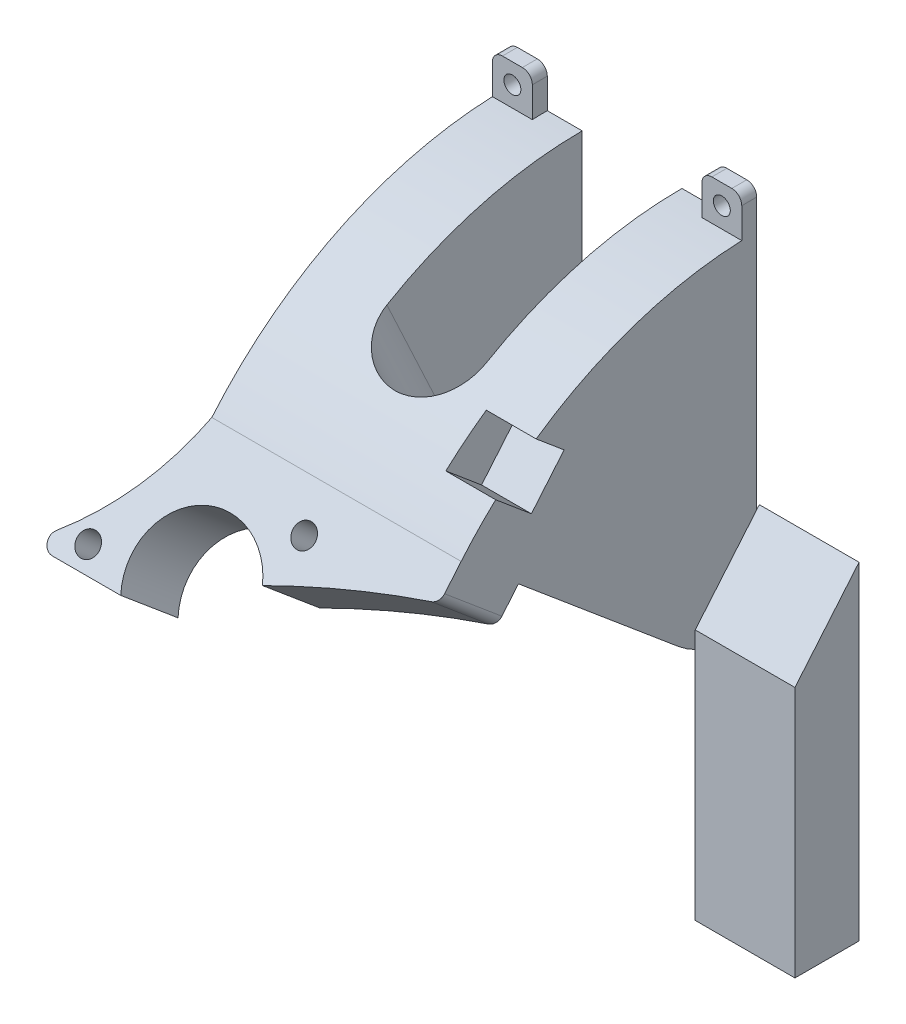
SolidWorks part; units mm, degrees
ref_plane "Ebene vorne" through (0, 0, 0) normal (0, 0, 1) x (1, 0, 0)
ref_plane "Ebene oben" through (0, 0, 0) normal (0, 1, 0) x (1, 0, 0)
ref_plane "Ebene rechts" through (0, 0, 0) normal (1, 0, 0) x (0, 0, -1)
sketch "Skizze1" plane through (0, 0, 0) normal (1, 0, 0) x (0, 0, -1)
  line L0 (0, 0) -> (0, 65.7804)
  line L1 (0, 0) -> (-12.8558, 0)
  line L2 (-12.8558, 0) -> (-12.8558, 50.4596)
  line L3 (-12.8558, 50.4596) -> (0, 65.7804)
  line L4 (-6.4279, 0) -> (-6.4279, 58.12) construction
  dimension "D1" = 50
  dimension "D2" = 20
  dimension "D3" = 58.12
extrude "Aufsatz-Linear austragen1" add sketch "Skizze1" along normal blind 20
ref_plane "Ebene1" through (0, 38.6015, -32.3905) normal (0, 0.766, -0.6428) x (-1, 0, 0)
sketch "Skizze2" plane through (0, 38.6015, -32.3905) normal (0, 0.766, -0.6428) x (-1, 0, 0)
  line L0 (-20, 42.2829) -> (0, 42.2829) construction
  line L1 (-10, 0) -> (-10, 83.3321) construction
  line L2 (-20, 0) -> (0, 0) construction
  line L3 (90, 60.5809) -> (90, 32.1579)
  line L4 (90, 32.1579) -> (40, 32.1579)
  line L5 (-110, 60.5809) -> (-110, 32.1579)
  line L6 (-60, 38.8503) -> (-60, 32.1579)
  line L7 (40, 38.8503) -> (40, 32.1579)
  line L8 (-60, 32.1579) -> (-110, 32.1579)
  arc A0 (-10, 42.2829) -> (98.0877, 78.3487) centre (-10, 222.2829) ccw construction
  arc A1 (-110, 60.5809) -> (-60, 38.8503) centre (-10, 222.2829) ccw
  arc A2 (40, 38.8503) -> (90, 60.5809) centre (-10, 222.2829) ccw
  point P15 (-10, 22.2829)
  dimension "D1" = 180
  dimension "D3" = 10.125
  dimension "D2" = 200
  dimension "D5" = 100
extrude "Aufsatz-Linear austragen2" add sketch "Skizze2" against normal blind 20
sketch "Skizze4" plane through (-90, 0, 0) normal (-1, 0, 0) x (0, 0, 1)
  line L0 (-7.7562, 59.2722) -> (14.0171, 77.5422) construction
  line L1 (-77.0542, 0) -> (77.0542, 0) construction
  line L2 (5.0996, 43.9513) -> (41.9791, 0)
  line L3 (5.0996, 43.9513) -> (-7.7562, 59.2722) construction
  line L4 (5.0996, 43.9513) -> (-7.7562, 59.2722)
  line L5 (-35.3953, 0) -> (-35.3953, 52.2205) construction
  line L6 (-35.3953, 0) -> (41.9791, 0)
  arc A0 (-7.7562, 59.2722) -> (-35.3953, 0) centre (41.9791, 0) ccw
  point P7 (0, 0)
  line M3 (-7.7562, 59.2722) -> (5.0996, 43.9513)
extrude "Aufsatz-Linear austragen3" add sketch "Skizze4" against normal blind 50 contours A0 L6 L2 M3 region at (-90, 21.1147, -3.3015)
sketch "Skizze6" plane through (0, 38.6015, -32.3905) normal (0, 0.766, -0.6428) x (1, 0, 0)
  line L0 (-90, -60.5809) -> (-109.0162, -60.5809)
  line L1 (-90, -32.1579) -> (-137.6907, -32.1579) construction
  line L2 (-90, -60.5809) -> (-90, -32.1579)
  line L3 (60, -32.1579) -> (-40, -32.1579) construction
  line L4 (10, -32.1579) -> (10, -107.2086) construction
  line L5 (-40, -38.8503) -> (-40, -32.1579)
  line L6 (-40, -32.1579) -> (-90, -32.1579)
  line L7 (-90, -32.1579) -> (-90, -60.5809)
  line L8 (-40, -38.8503) -> (-40, -32.1579)
  line L9 (-40, -32.1579) -> (-90, -32.1579)
  line L10 (110, -60.5809) -> (110, -32.1579)
  line L11 (110, -60.5809) -> (129.0162, -60.5809)
  arc A0 (-90, -32.1579) -> (-109.0162, -60.5809) centre (-144.3179, -16.3897) cw
  arc A1 (110, -32.1579) -> (129.0162, -60.5809) centre (164.3179, -16.3897) ccw
  arc A2 (-40, -38.8503) -> (-90, -60.5809) centre (10, -222.2829) ccw
  arc A3 (-40, -38.8503) -> (-90, -60.5809) centre (10, -222.2829) ccw
  line M9 (-90, -32.1579) -> (-90, -60.5809)
  dimension "D1" = 0
extrude "Aufsatz-Linear austragen4" add sketch "Skizze6" against normal blind 20 contours A0 L0 M9 | A1 L10 L11 region at (-95.6771, 72.2232, 7.6782) region at (115.6771, 72.2232, 7.6782)
fillet "Verrundung1" [suppressed] radius 3
sketch "Skizze5" plane through (0, 38.6015, -32.3905) normal (0, 0.766, -0.6428) x (1, 0, 0)
  line L0 (-79.5999, -54.5945) -> (-69.0166, -48.9382) construction
  line L1 (-79.5999, -54.5945) -> (-90.1831, -60.2508) construction
  line L2 (-79.5999, -54.5945) -> (-86.3975, -41.8758) construction
  line L3 (60, -32.1579) -> (-40, -32.1579) construction
  line L4 (10, -32.1579) -> (10, -101.6812) construction
  arc A0 (-90, -60.5809) -> (-68.8428, -49.2761) centre (-79.5999, -54.5945) cw
  arc A1 (-40, -38.8503) -> (-90, -60.5809) centre (10, -222.2829) ccw construction
  circle A2 centre (-67.9368, -39.2902) radius 2.25
  circle A3 centre (-98.8047, -55.7878) radius 2.25
  arc A4 (-40, -38.8503) -> (-90, -60.5809) centre (10, -222.2829) ccw construction
  arc A5 (110, -60.5809) -> (88.8428, -49.2761) centre (99.5999, -54.5945) ccw
  arc A6 (-90, -60.5809) -> (-68.8428, -49.2761) centre (-79.5999, -54.5945) ccw
  arc A7 (110, -60.5809) -> (88.8428, -49.2761) centre (99.5999, -54.5945) cw
  arc M4 (-90, -60.5809) -> (-40, -38.8503) centre (10, -222.2829) cw
  dimension "D1" = 12
  dimension "D5" = 4.5
  dimension "D2" = 0.38
  dimension "D3" = 35
  dimension "D4" = 8
extrude "Schnitt-Linear austragen1" cut sketch "Skizze5" against normal through all contours A0 M4 | A7 A5 region at (-81.9676, 70.8459, 6.0367) region at (99.5999, 73.6942, 9.4313)
sketch "Skizze7" plane through (60, 0, 0) normal (1, 0, 0) x (0, 0, -1)
  line L0 (7.7562, 59.2722) -> (-41.9791, 0)
  line L1 (-41.9791, 0) -> (35.3953, 0)
  arc A0 (7.7562, 59.2722) -> (35.3953, 0) centre (-41.9791, 0) cw
  arc A2 (35.3953, 0) -> (7.7562, 59.2722) centre (-41.9791, 0) ccw construction
extrude "Aufsatz-Linear austragen5" add sketch "Skizze7" along normal up to vertex (50 mm away) up to point (110, 43.9513, 5.0995)
ref_plane "Ebene5" [suppressed] through (10, 0, 0) normal (1, 0, 0) x (0, 0, -1)
sketch "Skizze9" plane through (0, 38.6015, -32.3905) normal (0, 0.766, -0.6428) x (1, 0, 0)
  line L0 (-55, -32.1579) -> (-55, -43.6141)
  line L1 (-40, -32.1579) -> (-90, -32.1579) construction
  line L2 (-40, -38.8503) -> (-40, -32.1579) construction
  line L6 (-109.0162, -60.5809) -> (-90, -60.5809)
  line L7 (-40, -38.8503) -> (-40, -32.1579)
  line L8 (-40, -32.1579) -> (-90, -32.1579)
  line L9 (-109.0162, -60.5809) -> (-90, -60.5809)
  line L11 (-55, -32.1579) -> (-90, -32.1579)
  arc A0 (-40, -38.8503) -> (-68.8428, -49.2761) centre (10, -222.2829) ccw construction
  arc A4 (-68.8428, -49.2761) -> (-90, -60.5809) centre (-79.5999, -54.5945) ccw
  arc A5 (-40, -38.8503) -> (-68.8428, -49.2761) centre (10, -222.2829) ccw
  arc A6 (-109.0162, -60.5809) -> (-90, -32.1579) centre (-144.3179, -16.3897) ccw
  arc A7 (-68.8428, -49.2761) -> (-90, -60.5809) centre (-79.5999, -54.5945) ccw
  arc A8 (-55, -43.6141) -> (-68.8428, -49.2761) centre (10, -222.2829) ccw
  arc A9 (-109.0162, -60.5809) -> (-90, -32.1579) centre (-144.3179, -16.3897) ccw
  dimension "D1" = 15
  dimension "D2" = 0
extrude "Aufsatz-Linear austragen6" [suppressed] add sketch "Skizze9" along normal blind 6
fillet "Verrundung2" [suppressed] radius 6
fillet "Verrundung3" radius 2 1 edges at (-109.0162, 69.8818, 20.445)
fillet "Verrundung4" [suppressed] radius 1
sketch "Skizze11" plane through (0, 23.2807, -19.5348) normal (0, -0.766, 0.6428) x (1, 0, 0)
  line L0 (60, 32.1579) -> (110, 32.1579)
  line L1 (110, 32.1579) -> (141.0282, 65.9)
  line L2 (141.0282, 65.9) -> (38.3436, 62.9928)
  line L3 (38.3436, 62.9928) -> (60, 32.1579)
  line L4 (-90, 32.1579) -> (-40, 32.1579)
  line L5 (-40, 32.1579) -> (-27.2753, 44.0032)
  line L6 (-27.2753, 44.0032) -> (-71.113, 77.6284)
  line L7 (-71.113, 77.6284) -> (-115.715, 75.5442)
  line L8 (-115.715, 75.5442) -> (-104.047, 34.6918)
  line L9 (-104.047, 34.6918) -> (-90, 32.1579)
extrude "Schnitt-Linear austragen3" cut sketch "Skizze11" against normal blind 5
ref_plane "Ebene6" through (0, 16.6209, -35.6436) normal (0, 0.4226, -0.9063) x (-1, 0, 0)
sketch "Skizze12" plane through (0, 16.6209, -35.6436) normal (0, 0.4226, -0.9063) x (-1, 0, 0)
  line L0 (75, -14.9587) -> (75, 35.0413)
  line L1 (40, -14.9587) -> (90, -14.9587) construction
  line L2 (75, 35.0413) -> (55, 35.0413)
  line L3 (55, 35.0413) -> (55, -14.9587)
  line L4 (55, -14.9587) -> (75, -14.9587)
  line L5 (40, 50.441) -> (40, -14.9587) construction
  line L6 (90, -14.9587) -> (90, 50.441) construction
  line L7 (40, -14.9587) -> (-60, -14.9587) construction
  line L8 (-10, -14.9587) -> (-10, 52.6156) construction
  line L9 (-75, -14.9587) -> (-95, -14.9587)
  line L10 (-75, 35.0413) -> (-75, -14.9587)
  line L11 (-95, -14.9587) -> (-95, 35.0413)
  line L12 (-95, 35.0413) -> (-75, 35.0413)
  dimension "D1" = 15
  dimension "D2" = 15
  dimension "D3" = 50
extrude "Schnitt-Linear austragen4" cut sketch "Skizze12" against normal through all
fillet "Verrundung5" radius 10 2 edges at (75, 39.4549, -1.6965) (95, 39.4549, -1.6965) tangent propagation no
fillet "Verrundung6" radius 10 2 edges at (-55, 39.4549, -1.6965) (-75, 39.4549, -1.6965)
sketch "Skizze13" plane through (0, 0, 0) normal (0, 1, 0) x (1, 0, 0)
  line L0 (-40, 35.3953) -> (-40, 43.3953)
  line L1 (-40, 43.3953) -> (-48, 43.3953)
  line L2 (-44, 39.3953) -> (-44, 35.3953) construction
  line L3 (-51.9152, 39.3953) -> (-40, 39.3953) construction
  line L4 (-40, 35.3953) -> (-55, 35.3953) construction
  line L5 (-48, 35.3953) -> (-48, 43.3953)
  line L6 (-55, 35.3953) -> (-75, 35.3953) construction
  line L7 (-65, 35.3953) -> (-65, 48.5338) construction
  line L8 (60, 35.3953) -> (-40, 35.3953) construction
  line L9 (10, 35.3953) -> (10, 91.6227) construction
  line L10 (-40, 35.3953) -> (-40, 33.3959)
  line L11 (-40, 35.3953) -> (-40, -41.9791) construction
  line L12 (-40, 33.3959) -> (-48, 33.3959)
  line L13 (-48, 33.3959) -> (-48, 35.3953)
  line L14 (-90, 43.3953) -> (-82, 43.3953)
  line L15 (-90, 35.3953) -> (-90, 43.3953)
  line L16 (-82, 35.3953) -> (-82, 43.3953)
  line L17 (-82, 33.3959) -> (-82, 35.3953)
  line L18 (-90, 35.3953) -> (-90, 33.3959)
  line L19 (-90, 33.3959) -> (-82, 33.3959)
  line L20 (71.9152, 39.3953) -> (60, 39.3953) construction
  line L21 (64, 39.3953) -> (64, 35.3953) construction
  line L22 (68, 33.3959) -> (68, 35.3953)
  line L23 (60, 33.3959) -> (68, 33.3959)
  line L24 (60, 35.3953) -> (60, 33.3959)
  line L25 (68, 35.3953) -> (68, 43.3953)
  line L26 (60, 43.3953) -> (68, 43.3953)
  line L27 (60, 35.3953) -> (60, 43.3953)
  line L28 (110, 33.3959) -> (102, 33.3959)
  line L29 (110, 35.3953) -> (110, 33.3959)
  line L30 (102, 33.3959) -> (102, 35.3953)
  line L31 (102, 35.3953) -> (102, 43.3953)
  line L32 (110, 35.3953) -> (110, 43.3953)
  line L33 (110, 43.3953) -> (102, 43.3953)
  circle A0 centre (-44, 39.3953) radius 1.7
  circle A1 centre (-86, 39.3953) radius 1.7
  circle A2 centre (64, 39.3953) radius 1.7
  circle A3 centre (106, 39.3953) radius 1.7
  dimension "D1" = 3.4
  dimension "D2" = 4
extrude "Aufsatz-Linear austragen9" add sketch "Skizze13" along normal blind 3
fillet "Verrundung7" radius 2 4 edges at (-40, 1.5, -43.3953) (-48, 1.5, -43.3953) (-82, 1.5, -43.3953) (-90, 1.5, -43.3953)
fillet "Verrundung8" radius 2 4 edges at (110, 1.5, -43.3953) (102, 1.5, -43.3953) (68, 1.5, -43.3953) (60, 1.5, -43.3953)
ref_plane "Ebene7" through (0, 3, 0) normal (0, -1, 0) x (-1, 0, 0)
sketch "Skizze14" plane through (0, 3, 0) normal (0, -1, 0) x (-1, 0, 0)
  line L0 (90, -32.9791) -> (75, -32.9791)
  line L1 (90, -1.8856) -> (90, -41.9791) construction
  line L2 (75, -41.9791) -> (75, -30.8758) construction
  line L3 (75, -32.9791) -> (75, -41.9791)
  line L4 (75, -41.9791) -> (90, -41.9791)
  line L5 (90, -41.9791) -> (90, -32.9791)
  line L6 (75, -41.9791) -> (55, -41.9791) construction
  line L7 (65, -41.9791) -> (65, -28.0183) construction
  line L8 (40, -41.9791) -> (-60, -41.9791) construction
  line L9 (-10, -41.9791) -> (-10, -6.4616) construction
  line L10 (40, -41.9791) -> (40, -32.9791)
  line L11 (55, -41.9791) -> (40, -41.9791)
  line L12 (55, -32.9791) -> (55, -41.9791)
  line L13 (40, -32.9791) -> (55, -32.9791)
  line L14 (-60, -32.9791) -> (-75, -32.9791)
  line L15 (-75, -32.9791) -> (-75, -41.9791)
  line L16 (-75, -41.9791) -> (-60, -41.9791)
  line L17 (-60, -41.9791) -> (-60, -32.9791)
  line L18 (-110, -41.9791) -> (-110, -32.9791)
  line L19 (-95, -41.9791) -> (-110, -41.9791)
  line L20 (-95, -32.9791) -> (-95, -41.9791)
  line L21 (-110, -32.9791) -> (-95, -32.9791)
  dimension "D1" = 9
extrude "Schnitt-Linear austragen5" cut sketch "Skizze14" against normal through all
fillet "Verrundung9" radius 18 2 edges at (-47.5, 10.7258, 32.9791) (-82.5, 10.7258, 32.9791)
sketch "Skizze15" plane through (0, 3, 0) normal (0, -1, 0) x (-1, 0, 0)
  line L0 (90, -36.2204) -> (75, -36.2204) construction
  line L1 (90, -39.4618) -> (90, -32.9791) construction
  line L2 (75, -32.9791) -> (75, -39.4618) construction
  line L3 (75, -41.9791) -> (55, -41.9791) construction
  line L4 (65, -41.9791) -> (65, -29.984) construction
  line L5 (40, -41.9791) -> (-60, -41.9791) construction
  line L6 (-10, -41.9791) -> (-10, -7.0981) construction
  circle A0 centre (82.5, -36.2204) radius 1.7
  circle A1 centre (47.5, -36.2204) radius 1.7
  circle A2 centre (-102.5, -36.2204) radius 1.7
  circle A3 centre (-67.5, -36.2204) radius 1.7
  dimension "D1" = 3.4
extrude "Schnitt-Linear austragen6" cut sketch "Skizze15" along normal through all
fillet "Verrundung10" radius 2 2 edges at (129.0162, 71.7969, 18.838) (60, 57.8287, 2.1914)
sketch "Skizze17" plane through (0, 38.6015, -32.3905) normal (0, 0.766, -0.6428) x (1, 0, 0)
  line L0 (10, -222.2829) -> (73.4967, -26.8602) construction
  line L1 (10, -222.2829) -> (10, -14.9353) construction
  line L2 (110, -32.1579) -> (60, -32.1579) construction
  line L3 (66.518, -32.1579) -> (64.0133, -39.8666)
  line L4 (64.0133, -39.8666) -> (61.1602, -38.9395)
  line L5 (61.1602, -38.9395) -> (63.3637, -32.1579)
  line L6 (63.3637, -32.1579) -> (66.518, -32.1579)
  line L7 (77.0327, -32.1579) -> (73.5239, -42.9568)
  line L8 (73.5239, -42.9568) -> (76.3771, -43.8838)
  line L9 (76.3771, -43.8838) -> (80.1871, -32.1579)
  line L10 (80.1871, -32.1579) -> (77.0327, -32.1579)
  dimension "D2" = 10
  dimension "D3" = 3
  dimension "D4" = 3
extrude "Aufsatz-Linear austragen10" [suppressed] add sketch "Skizze17" along normal blind 5
fillet "Verrundung11" [suppressed] radius 4
ref_plane "Ebene8" through (0, 38.6015, -32.3905) normal (0, 0.766, -0.6428) x (1, 0, 0)
sketch "Skizze10" plane through (0, 38.6015, -32.3905) normal (0, 0.766, -0.6428) x (1, 0, 0)
  line L0 (60, -32.1579) -> (-40, -32.1579) construction
  line L1 (110, -60.5809) -> (123.7074, -60.5809) construction
  line L2 (10, -32.1579) -> (10, -49.3349) construction
  circle A0 centre (99.5999, -54.5945) radius 19.6 construction
  circle A1 centre (86.348, -40.1533) radius 2.25
  circle A2 centre (119.0989, -56.5809) radius 2.25
  circle A3 centre (-66.348, -40.1533) radius 2.25
  circle A4 centre (-99.0989, -56.5809) radius 2.25
  dimension "D1" = 39.2
  dimension "D2" = 4.5
  dimension "D3" = 36.64
  dimension "D4" = 4
extrude "Schnitt-Linear austragen2" cut sketch "Skizze10" against normal through all contours A2 | A1 | A3 | A4 region at (86.348, 64.4116, -1.6313) region at (119.0989, 74.9711, 10.953) region at (-66.348, 64.4116, -1.6313) region at (-99.0989, 74.9711, 10.953)
sketch "Skizze18" plane through (0, 38.6015, -32.3905) normal (0, 0.766, -0.6428) x (1, 0, 0)
  line L0 (60, -25.4892) -> (-40, -25.4892) construction
  line L1 (60, 25.1414) -> (60, -32.1579) construction
  line L2 (-40, -32.1579) -> (-40, 25.1414) construction
  line L3 (10, -25.4892) -> (10, 9.2287) construction
  line L4 (-50, -22.1579) -> (70, -22.1579)
  line L5 (-50, -22.1579) -> (-50, -11.9579)
  line L6 (-50, -11.9579) -> (70, -11.9579)
  line L7 (70, -22.1579) -> (70, -11.9579)
  line L9 (110, -32.1579) -> (60, -32.1579) construction
  point P13 (10, -11.9579)
  point P14 (10, -22.1579)
  dimension "D1" = 10.2
  dimension "D2" = 120
  dimension "D3" = 10
extrude "Schnitt-Linear austragen8" cut sketch "Skizze18" against normal blind 10
fillet "Verrundung12" radius 18 2 edges at (102.5, 10.7258, 32.9791) (67.5, 10.7258, 32.9791)
fillet "Verrundung13" radius 2 1 edges at (-40, 57.8287, 2.1914)
sketch "Skizze16" plane through (60, 0, 0) normal (1, 0, 0) x (0, 0, -1)
  circle A0 centre (7.4883, 22.2505) radius 102.0124
extrude "Schnitt-Linear austragen9" cut sketch "Skizze16" along normal through all
move or copy body "Körper-Verschieben/Kopieren1" bodies to move or copy 129 copy no rotation origin (0, 38.7711, -0.7081) rotation axis (1, 0, 0) rotation angle 90
